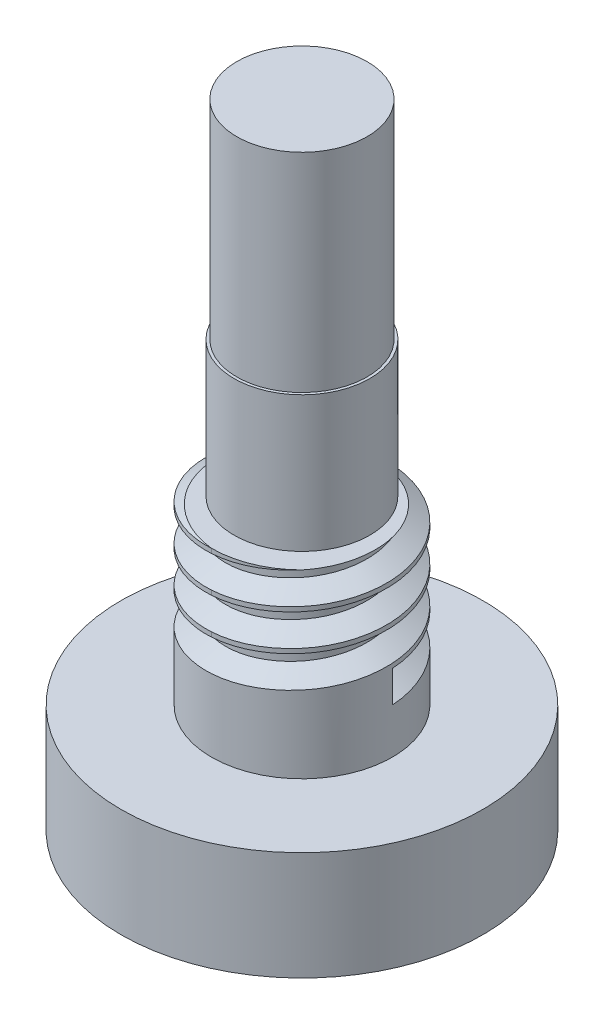
SolidWorks part; units mm, degrees
ref_plane "Front Plane" through (0, 0, 0) normal (0, 0, 1) x (1, 0, 0)
ref_plane "Top Plane" through (0, 0, 0) normal (0, 1, 0) x (1, 0, 0)
ref_plane "Right Plane" through (0, 0, 0) normal (1, 0, 0) x (0, 0, -1)
sketch "Sketch1" plane through (0, 0, 0) normal (0, 1, 0) x (1, 0, 0)
  circle A0 centre (0, 0) radius 2.286
  dimension "D1" = 4.572
extrude "Boss-Extrude1" add sketch "Sketch1" along normal blind 7.3025
sketch "Sketch2" plane through (0, 0, 0) normal (0, -1, 0) x (-1, 0, 0)
  circle A0 centre (0, 0) radius 2.3825
  dimension "D1" = 4.765
extrude "Boss-Extrude2" add sketch "Sketch2" along normal blind 4.7622
sketch "Sketch3" plane through (0, -4.7622, 0) normal (0, -1, 0) x (-1, 0, 0)
  circle A0 centre (0, 0) radius 3.175
  dimension "D1" = 6.35
extrude "Boss-Extrude3" add sketch "Sketch3" along normal blind 3.175
sketch "Sketch4" plane through (0, -7.9372, 0) normal (0, -1, 0) x (-1, 0, 0)
  circle A0 centre (0, 0) radius 3.175
  dimension "D1" = 6.35
extrude "Boss-Extrude4" add sketch "Sketch4" along normal blind 3.175
thread "Thread2" pitch 1.27 method cut profile "Thread Profile3" start angle 0, offset 1.5875, length 0, pitch 1.27, diameter 6.35
ref_plane "Plane3" through (3.175, -9.5247, 0) normal (0, 0, 1) x (1, 0, 0)
sketch "Thread Profile3" plane through (3.175, -9.5247, 0) normal (0, 0, 1) x (1, 0, 0)
  line L0 (0, 0) -> (0, 1.27) construction
  line L11 (0, 0) -> (0, 1.1112)
  line L12 (0, 1.1112) -> (-0.6874, 0.7144)
  line L13 (-0.6874, 0.7144) -> (-0.6874, 0.3969)
  line L15 (-0.6874, 0.3969) -> (0, 0)
  line L17 (-0.6874, 0.5556) -> (0, 0.5556) construction
  point P2 (0, 0)
  dimension "Pitch" = 1.27
  dimension "Profile_Angle" = 60
  dimension "Profile_Land" = 0.3175
  dimension "Profile_Height" = 0.6874
sketch "Sketch11" plane through (0, -11.1122, 0) normal (0, -1, 0) x (-1, 0, 0)
  circle A0 centre (0, 0) radius 6.35
  dimension "D1" = 12.7
extrude "Boss-Extrude5" add sketch "Sketch11" along normal blind 3.81
fillet "Fillet1" [suppressed] radius 2.54
